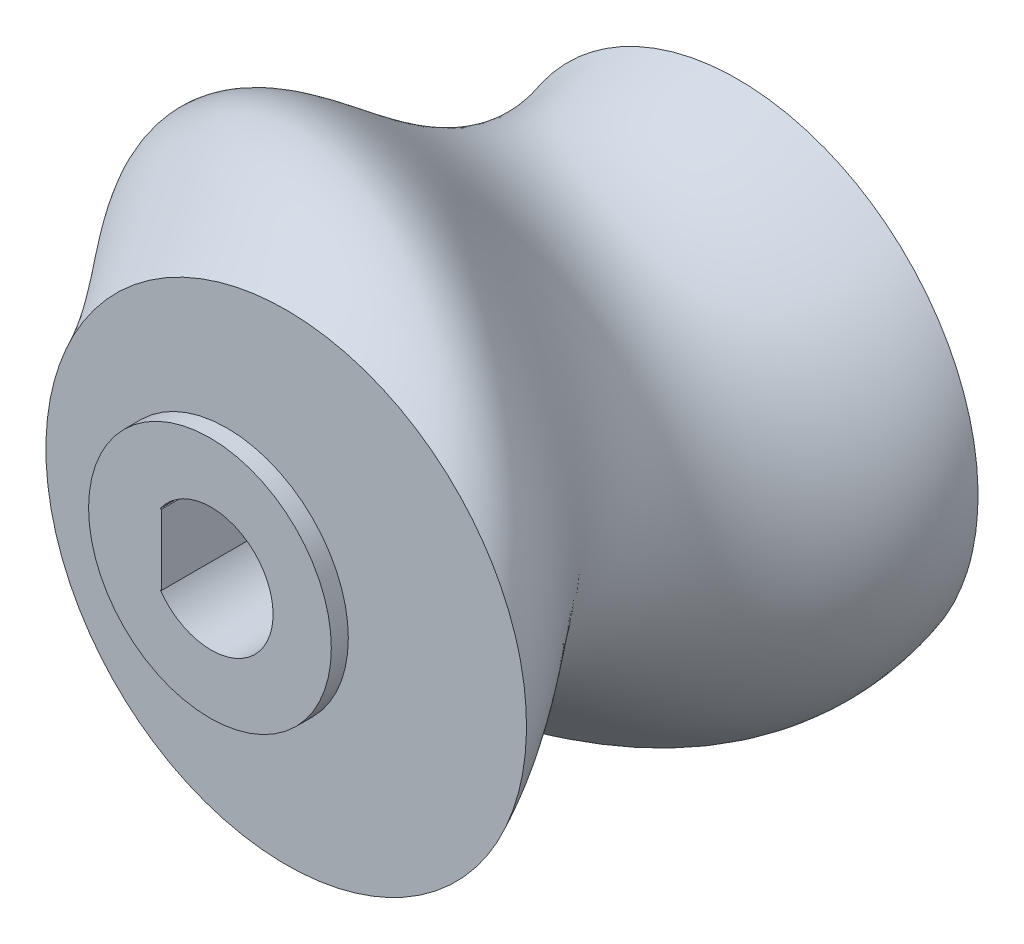
SolidWorks part; units mm, degrees
ref_plane "Ebene vorne" through (0, 0, 0) normal (0, 0, 1) x (1, 0, 0)
ref_plane "Ebene oben" through (0, 0, 0) normal (0, 1, 0) x (1, 0, 0)
ref_plane "Ebene rechts" through (0, 0, 0) normal (1, 0, 0) x (0, 0, -1)
sketch "Skizze2" plane through (0, 0, 0) normal (0, 0, 1) x (1, 0, 0)
  circle A0 centre (0, 0) radius 9.8996
  dimension "D1" = 19.7991
ref_plane "Ebene1" through (0, 0, 0) normal (0, 0, 1) x (1, 0, 0)
sketch "Skizze3" plane through (0, 0, 0) normal (0, 0, 1) x (1, 0, 0)
  circle A0 centre (-2.45, 0) radius 2.55
  point P0 (-2.45, 0)
  dimension "D2" = 5.1
  dimension "D1" = 2.45
curve "Spirale/Helix1" pitch 20 height 20 radius 2.55 left hand yes centre (-2.45, 0, 0) axis (0, 0, 1) start towards (1, 0, 0)
sweep "Austragung1" add profiles "Skizze2" path "Spirale/Helix1"
sketch "Skizze5" plane through (0, 0, 20) normal (0, 0, 1) x (1, 0, 0)
  circle A0 centre (0, 0) radius 2.5
  dimension "D1" = 5
ref_plane "Ebene3" through (0.1, 0, 0) normal (0, -0.6252, 0.7804) x (1, 0, 0)
extrude "Schnitt-Linear austragen2" cut sketch "Skizze3<2>" along normal blind 27
sketch "Skizze3<2>" plane through (0, 0, 0) normal (0, 0, 1) x (1, 0, 0) same geometry as "Skizze3"
ref_axis "Achse2" through (-2.45, 0, 72.3086) along (0, 0, -1)
sketch "Skizze6" plane through (0, 0, 20) normal (0, 0, 1) x (1, 0, 0)
  circle A0 centre (-2.5, 0) radius 5
  circle A1 centre (0, 0) radius 2.5 construction
  circle A2 centre (-2.5, 0) radius 12.7429
extrude "Schnitt-Linear austragen3" cut sketch "Skizze6" against normal blind 0.7
sketch "Skizze7" plane through (0, 0, 0) normal (0, 0, -1) x (-1, 0, 0)
  circle A0 centre (2.5, 0) radius 5
  circle A1 centre (0, 0) radius 2.5 construction
  circle A2 centre (2.5, 0) radius 13.0245
extrude "Schnitt-Linear austragen4" cut sketch "Skizze7" against normal blind 0.7
sketch "Skizze8" plane through (0, 0, 0) normal (0, 0, -1) x (-1, 0, 0)
  line L0 (50, 0) -> (-50, 0) construction
  line L1 (5.5, 1.4486) -> (4.5, 1.4486)
  line L2 (5.5, 1.4486) -> (5.5, -1.4486)
  line L3 (5.5, -1.4486) -> (4.5, -1.4486)
  line L4 (4.5, 1.4486) -> (4.5, -1.4486)
  line L5 (5.5, 1.4486) -> (4.5, -1.4486) construction
  line L6 (5.5, -1.4486) -> (4.5, 1.4486) construction
  circle A0 centre (2.45, 0) radius 2.55 construction
  point P0 (5, 0)
  dimension "D1" = 0.5
extrude "Aufsatz-Linear austragen1" add sketch "Skizze8" against normal blind 20
